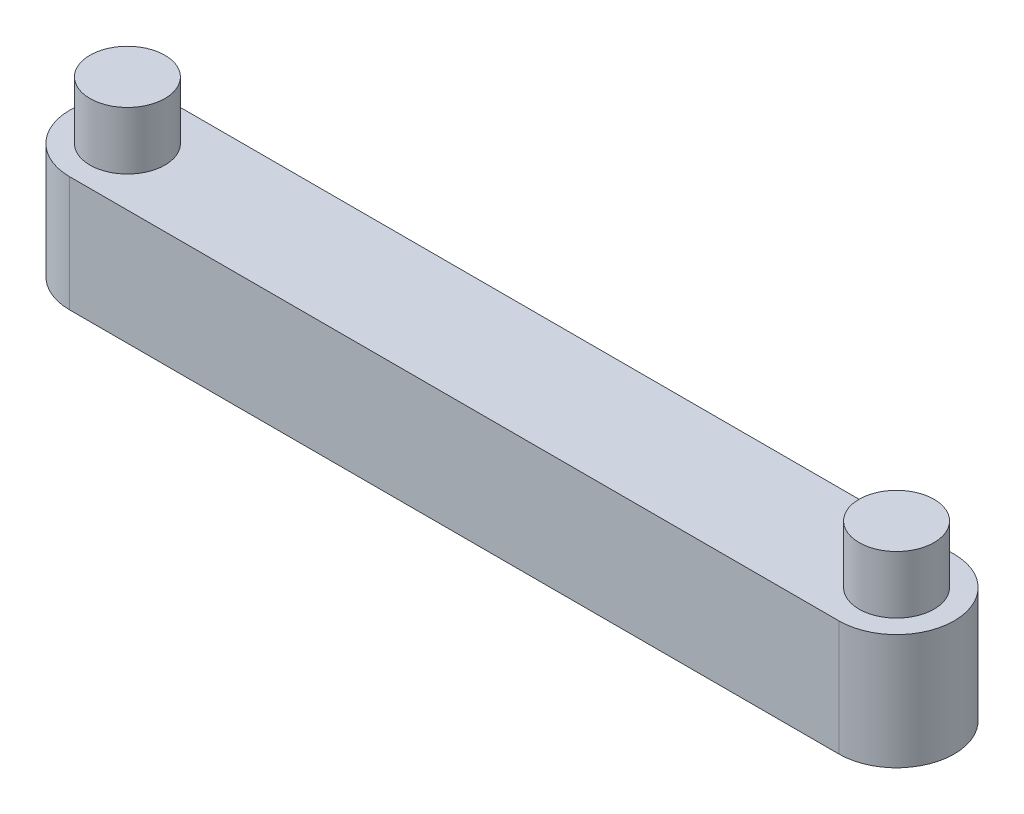
SolidWorks part; units mm, degrees
ref_plane "Front Plane" through (0, 0, 0) normal (0, 0, 1) x (1, 0, 0)
ref_plane "Top Plane" through (0, 0, 0) normal (0, 1, 0) x (1, 0, 0)
ref_plane "Right Plane" through (0, 0, 0) normal (1, 0, 0) x (0, 0, -1)
sketch "Sketch1" plane through (0, 0, 0) normal (0, 1, 0) x (1, 0, 0)
  line L0 (-100, 0) -> (100, 0) construction
  line L1 (-100, 15) -> (100, 15)
  line L2 (-100, -15) -> (100, -15)
  arc A0 (-100, 15) -> (-100, -15) centre (-100, 0) ccw
  arc A1 (100, -15) -> (100, 15) centre (100, 0) ccw
  point P2 (0, 0)
  dimension "D2" = 15
  dimension "D1" = 200
extrude "Boss-Extrude1" add sketch "Sketch1" along normal mid plane 30
sketch "Sketch2" plane through (0, 0, 0) normal (0, 1, 0) x (1, 0, 0)
  circle A0 centre (100, 0) radius 9.75
  circle A1 centre (-100, 0) radius 9.75
  dimension "D1" = 19.5
  dimension "D2" = 19.5
extrude "Cut-Extrude1" cut sketch "Sketch2" against normal through all
extrude "Boss-Extrude2" add sketch "Sketch2<2>" along normal blind 30
sketch "Sketch2<2>" plane through (0, 0, 0) normal (0, 1, 0) x (1, 0, 0) same geometry as "Sketch2"
extrude "Boss-Extrude3" add sketch "Sketch2<3>" against normal blind 3
sketch "Sketch2<3>" plane through (0, 0, 0) normal (0, 1, 0) x (1, 0, 0) same geometry as "Sketch2"
